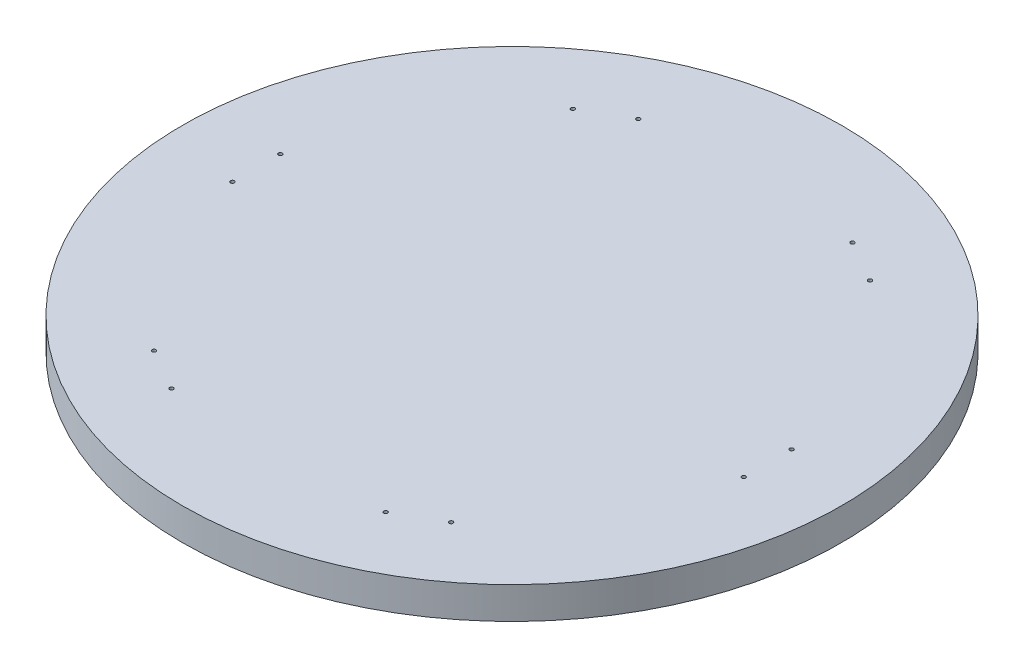
SolidWorks part; units mm, degrees
ref_plane "Front Plane" through (0, 0, 0) normal (0, 0, 1) x (1, 0, 0)
ref_plane "Top Plane" through (0, 0, 0) normal (0, 1, 0) x (1, 0, 0)
ref_plane "Right Plane" through (0, 0, 0) normal (1, 0, 0) x (0, 0, -1)
sketch "Sketch1" plane through (0, 0, 0) normal (0, 1, 0) x (1, 0, 0)
  circle A0 centre (0, 0) radius 261.9375
extrude "Boss-Extrude1" add sketch "Sketch1" along normal blind 25.4
sketch "Sketch6" plane through (0, 0, 0) normal (0, -1, 0) x (1, 0, 0)
  line L0 (203.2, 19.05) -> (203.2, -19.05) construction
  line L1 (215.9, 19.05) -> (215.9, -19.05)
  line L2 (190.5, 19.05) -> (190.5, -19.05)
  line L3 (203.2, -16.5451) -> (201.0307, -17.7976) construction
  line L4 (201.0307, -17.7976) -> (201.0307, -20.3024) construction
  line L5 (201.0307, -20.3024) -> (203.2, -21.5549) construction
  line L6 (203.2, -21.5549) -> (205.3693, -20.3024) construction
  line L7 (205.3693, -20.3024) -> (205.3693, -17.7976) construction
  line L8 (205.3693, -17.7976) -> (203.2, -16.5451) construction
  line L9 (203.2, 22.1294) -> (201.0307, 20.8769) construction
  line L10 (201.0307, 20.8769) -> (201.0307, 18.372) construction
  line L11 (201.0307, 18.372) -> (203.2, 17.1196) construction
  line L12 (203.2, 17.1196) -> (205.3693, 18.372) construction
  line L13 (205.3693, 18.372) -> (205.3693, 20.8769) construction
  line L14 (205.3693, 20.8769) -> (203.2, 22.1294) construction
  line L15 (0, 0) -> (203.2, 0) construction
  line L16 (87.2715, -184.2489) -> (85.1022, -182.9965) construction
  line L17 (85.1022, -182.9965) -> (82.9329, -184.2489) construction
  line L18 (82.9329, -184.2489) -> (82.9329, -186.7538) construction
  line L19 (82.9329, -186.7538) -> (85.1022, -188.0063) construction
  line L20 (85.1022, -188.0063) -> (87.2715, -186.7538) construction
  line L21 (87.2715, -186.7538) -> (87.2715, -184.2489) construction
  line L22 (120.7646, -164.9117) -> (118.5953, -163.6592) construction
  line L23 (118.5953, -163.6592) -> (116.426, -164.9117) construction
  line L24 (116.426, -164.9117) -> (116.426, -167.4166) construction
  line L25 (116.426, -167.4166) -> (118.5953, -168.669) construction
  line L26 (118.5953, -168.669) -> (120.7646, -167.4166) construction
  line L27 (120.7646, -167.4166) -> (120.7646, -164.9117) construction
  line L28 (0, 0) -> (101.6, -175.9764) construction
  line L29 (118.0978, -166.4514) -> (85.1022, -185.5014) construction
  line L30 (124.4478, -177.4499) -> (91.4522, -196.4999)
  line L31 (111.7478, -155.4528) -> (78.7522, -174.5028)
  line L32 (-115.9285, -167.7038) -> (-115.9285, -165.1989) construction
  line L33 (-115.9285, -165.1989) -> (-118.0978, -163.9465) construction
  line L34 (-118.0978, -163.9465) -> (-120.2671, -165.1989) construction
  line L35 (-120.2671, -165.1989) -> (-120.2671, -167.7038) construction
  line L36 (-120.2671, -167.7038) -> (-118.0978, -168.9563) construction
  line L37 (-118.0978, -168.9563) -> (-115.9285, -167.7038) construction
  line L38 (-82.4354, -187.0411) -> (-82.4354, -184.5362) construction
  line L39 (-82.4354, -184.5362) -> (-84.6047, -183.2837) construction
  line L40 (-84.6047, -183.2837) -> (-86.774, -184.5362) construction
  line L41 (-86.774, -184.5362) -> (-86.774, -187.0411) construction
  line L42 (-86.774, -187.0411) -> (-84.6047, -188.2935) construction
  line L43 (-84.6047, -188.2935) -> (-82.4354, -187.0411) construction
  line L44 (0, 0) -> (-101.6, -175.9764) construction
  line L45 (-85.1022, -185.5014) -> (-118.0978, -166.4514) construction
  line L46 (-91.4522, -196.4999) -> (-124.4478, -177.4499)
  line L47 (-78.7522, -174.5028) -> (-111.7478, -155.4528)
  line L48 (-203.2, 16.5451) -> (-201.0307, 17.7976) construction
  line L49 (-201.0307, 17.7976) -> (-201.0307, 20.3024) construction
  line L50 (-201.0307, 20.3024) -> (-203.2, 21.5549) construction
  line L51 (-203.2, 21.5549) -> (-205.3693, 20.3024) construction
  line L52 (-205.3693, 20.3024) -> (-205.3693, 17.7976) construction
  line L53 (-205.3693, 17.7976) -> (-203.2, 16.5451) construction
  line L54 (-203.2, -22.1294) -> (-201.0307, -20.8769) construction
  line L55 (-201.0307, -20.8769) -> (-201.0307, -18.372) construction
  line L56 (-201.0307, -18.372) -> (-203.2, -17.1196) construction
  line L57 (-203.2, -17.1196) -> (-205.3693, -18.372) construction
  line L58 (-205.3693, -18.372) -> (-205.3693, -20.8769) construction
  line L59 (-205.3693, -20.8769) -> (-203.2, -22.1294) construction
  line L60 (0, 0) -> (-203.2, 0) construction
  line L61 (-203.2, -19.05) -> (-203.2, 19.05) construction
  line L62 (-215.9, -19.05) -> (-215.9, 19.05)
  line L63 (-190.5, -19.05) -> (-190.5, 19.05)
  line L64 (-87.2715, 184.2489) -> (-85.1022, 182.9965) construction
  line L65 (-85.1022, 182.9965) -> (-82.9329, 184.2489) construction
  line L66 (-82.9329, 184.2489) -> (-82.9329, 186.7538) construction
  line L67 (-82.9329, 186.7538) -> (-85.1022, 188.0063) construction
  line L68 (-85.1022, 188.0063) -> (-87.2715, 186.7538) construction
  line L69 (-87.2715, 186.7538) -> (-87.2715, 184.2489) construction
  line L70 (-120.7646, 164.9117) -> (-118.5953, 163.6592) construction
  line L71 (-118.5953, 163.6592) -> (-116.426, 164.9117) construction
  line L72 (-116.426, 164.9117) -> (-116.426, 167.4166) construction
  line L73 (-116.426, 167.4166) -> (-118.5953, 168.669) construction
  line L74 (-118.5953, 168.669) -> (-120.7646, 167.4166) construction
  line L75 (-120.7646, 167.4166) -> (-120.7646, 164.9117) construction
  line L76 (0, 0) -> (-101.6, 175.9764) construction
  line L77 (-118.0978, 166.4514) -> (-85.1022, 185.5014) construction
  line L78 (-124.4478, 177.4499) -> (-91.4522, 196.4999)
  line L79 (-111.7478, 155.4528) -> (-78.7522, 174.5028)
  line L80 (115.9285, 167.7038) -> (115.9285, 165.1989) construction
  line L81 (115.9285, 165.1989) -> (118.0978, 163.9465) construction
  line L82 (118.0978, 163.9465) -> (120.2671, 165.1989) construction
  line L83 (120.2671, 165.1989) -> (120.2671, 167.7038) construction
  line L84 (120.2671, 167.7038) -> (118.0978, 168.9563) construction
  line L85 (118.0978, 168.9563) -> (115.9285, 167.7038) construction
  line L86 (82.4354, 187.0411) -> (82.4354, 184.5362) construction
  line L87 (82.4354, 184.5362) -> (84.6047, 183.2837) construction
  line L88 (84.6047, 183.2837) -> (86.774, 184.5362) construction
  line L89 (86.774, 184.5362) -> (86.774, 187.0411) construction
  line L90 (86.774, 187.0411) -> (84.6047, 188.2935) construction
  line L91 (84.6047, 188.2935) -> (82.4354, 187.0411) construction
  line L92 (0, 0) -> (101.6, 175.9764) construction
  line L93 (85.1022, 185.5014) -> (118.0978, 166.4514) construction
  line L94 (91.4522, 196.4999) -> (124.4478, 177.4499)
  line L95 (78.7522, 174.5028) -> (111.7478, 155.4528)
  arc A0 (215.9, 19.05) -> (190.5, 19.05) centre (203.2, 19.05) ccw
  arc A1 (190.5, -19.05) -> (215.9, -19.05) centre (203.2, -19.05) ccw
  circle A2 centre (203.2, -19.05) radius 2.1693 construction
  circle A3 centre (203.2, 19.6245) radius 2.1693 construction
  circle A4 centre (203.2, -19.05) radius 1.524 construction
  circle A5 centre (203.2, 19.6245) radius 1.524 construction
  circle A6 centre (85.1022, -185.5014) radius 2.1693 construction
  circle A7 centre (118.5953, -166.1641) radius 2.1693 construction
  circle A8 centre (85.1022, -185.5014) radius 1.524 construction
  circle A9 centre (118.5953, -166.1641) radius 1.524 construction
  arc A10 (124.4478, -177.4499) -> (111.7478, -155.4528) centre (118.0978, -166.4514) ccw
  arc A11 (78.7522, -174.5028) -> (91.4522, -196.4999) centre (85.1022, -185.5014) ccw
  circle A12 centre (-118.0978, -166.4514) radius 2.1693 construction
  circle A13 centre (-84.6047, -185.7886) radius 2.1693 construction
  circle A14 centre (-118.0978, -166.4514) radius 1.524 construction
  circle A15 centre (-84.6047, -185.7886) radius 1.524 construction
  arc A16 (-91.4522, -196.4999) -> (-78.7522, -174.5028) centre (-85.1022, -185.5014) ccw
  arc A17 (-111.7478, -155.4528) -> (-124.4478, -177.4499) centre (-118.0978, -166.4514) ccw
  circle A18 centre (-203.2, 19.05) radius 2.1693 construction
  circle A19 centre (-203.2, -19.6245) radius 2.1693 construction
  circle A20 centre (-203.2, 19.05) radius 1.524 construction
  circle A21 centre (-203.2, -19.6245) radius 1.524 construction
  arc A22 (-215.9, -19.05) -> (-190.5, -19.05) centre (-203.2, -19.05) ccw
  arc A23 (-190.5, 19.05) -> (-215.9, 19.05) centre (-203.2, 19.05) ccw
  circle A24 centre (-85.1022, 185.5014) radius 2.1693 construction
  circle A25 centre (-118.5953, 166.1641) radius 2.1693 construction
  circle A26 centre (-85.1022, 185.5014) radius 1.524 construction
  circle A27 centre (-118.5953, 166.1641) radius 1.524 construction
  arc A28 (-124.4478, 177.4499) -> (-111.7478, 155.4528) centre (-118.0978, 166.4514) ccw
  arc A29 (-78.7522, 174.5028) -> (-91.4522, 196.4999) centre (-85.1022, 185.5014) ccw
  circle A30 centre (118.0978, 166.4514) radius 2.1693 construction
  circle A31 centre (84.6047, 185.7886) radius 2.1693 construction
  circle A32 centre (118.0978, 166.4514) radius 1.524 construction
  circle A33 centre (84.6047, 185.7886) radius 1.524 construction
  arc A34 (91.4522, 196.4999) -> (78.7522, 174.5028) centre (85.1022, 185.5014) ccw
  arc A35 (111.7478, 155.4528) -> (124.4478, 177.4499) centre (118.0978, 166.4514) ccw
  point P2 (203.2, 0)
  point P32 (101.6, -175.9764)
  point P58 (-101.6, -175.9764)
  point P84 (-203.2, 0)
  point P110 (-101.6, 175.9764)
  point P136 (101.6, 175.9764)
  point P160 (0, 0)
  dimension "D1" = 6
extrude "Cut-Extrude4" cut sketch "Sketch6" against normal blind 12.7
sketch "Sketch9" plane through (0, 0, 0) normal (0, -1, 0) x (1, 0, 0)
  circle A0 centre (0, 0) radius 25.4
extrude "Boss-Extrude2" add sketch "Sketch9" along normal blind 10.16 and the other way through all
sketch "Sketch10" plane through (0, -10.16, 0) normal (0, -1, 0) x (1, 0, 0)
  line L0 (0, -2.032) -> (0, 1.524) construction
  line L1 (-1.344, 1.524) -> (1.344, 1.524)
  line L2 (-2.032, 0) -> (-2.032, 1.524)
  line L3 (-2.032, 1.524) -> (-1.344, 1.524)
  line L4 (2.032, 0) -> (2.032, 1.524)
  line L5 (2.032, 1.524) -> (1.344, 1.524)
  arc A0 (-2.032, 0) -> (2.032, 0) centre (0, 0) ccw
extrude "Cut-Extrude7" cut sketch "Sketch10" against normal blind 19.05
sketch "Sketch11" plane through (0, 0, 0) normal (0, -1, 0) x (1, 0, 0)
  line L0 (0, 0) -> (-11.1642, -177.4492) construction
  line L1 (0, 0) -> (0, -291.8902) construction
  line L2 (0, 0) -> (11.1642, -177.4492) construction
  line L3 (-33.3164, -174.6507) -> (-22.2403, -176.0499) construction
  line L4 (-11.1642, -177.4492) -> (0, -177.4492) construction
  line L5 (0, -177.4492) -> (11.1642, -177.4492) construction
  line L6 (-22.2403, -176.0499) -> (-11.1642, -177.4492) construction
  line L7 (-54.9432, -169.0978) -> (-44.1298, -171.8743) construction
  line L8 (-44.1298, -171.8743) -> (-33.3164, -174.6507) construction
  line L9 (-75.7036, -160.8782) -> (-65.3234, -164.988) construction
  line L10 (-65.3234, -164.988) -> (-54.9432, -169.0978) construction
  line L11 (-95.27, -150.1215) -> (-85.4868, -155.4999) construction
  line L12 (-85.4868, -155.4999) -> (-75.7036, -160.8782) construction
  line L13 (-113.334, -136.9973) -> (-104.302, -143.5594) construction
  line L14 (-104.302, -143.5594) -> (-95.27, -150.1215) construction
  line L15 (-129.6106, -121.7125) -> (-121.4723, -129.3549) construction
  line L16 (-121.4723, -129.3549) -> (-113.334, -136.9973) construction
  line L17 (-143.8432, -104.5082) -> (-136.7269, -113.1103) construction
  line L18 (-136.7269, -113.1103) -> (-129.6106, -121.7125) construction
  line L19 (-155.8073, -85.6558) -> (-149.8253, -95.082) construction
  line L20 (-149.8253, -95.082) -> (-143.8432, -104.5082) construction
  line L21 (-165.3143, -65.4525) -> (-160.5608, -75.5542) construction
  line L22 (-160.5608, -75.5542) -> (-155.8073, -85.6558) construction
  line L23 (-172.2141, -44.2171) -> (-168.7642, -54.8348) construction
  line L24 (-168.7642, -54.8348) -> (-165.3143, -65.4525) construction
  line L25 (-176.398, -22.2842) -> (-174.306, -33.2507) construction
  line L26 (-174.306, -33.2507) -> (-172.2141, -44.2171) construction
  line L27 (-177.8, 0) -> (-177.099, -11.1421) construction
  line L28 (-177.099, -11.1421) -> (-176.398, -22.2842) construction
  line L29 (-176.398, 22.2842) -> (-177.099, 11.1421) construction
  line L30 (-177.099, 11.1421) -> (-177.8, 0) construction
  line L31 (-172.2141, 44.2171) -> (-174.306, 33.2507) construction
  line L32 (-174.306, 33.2507) -> (-176.398, 22.2842) construction
  line L33 (-165.3143, 65.4525) -> (-168.7642, 54.8348) construction
  line L34 (-168.7642, 54.8348) -> (-172.2141, 44.2171) construction
  line L35 (-155.8073, 85.6558) -> (-160.5608, 75.5542) construction
  line L36 (-160.5608, 75.5542) -> (-165.3143, 65.4525) construction
  line L37 (-143.8432, 104.5082) -> (-149.8253, 95.082) construction
  line L38 (-149.8253, 95.082) -> (-155.8073, 85.6558) construction
  line L39 (-129.6106, 121.7125) -> (-136.7269, 113.1103) construction
  line L40 (-136.7269, 113.1103) -> (-143.8432, 104.5082) construction
  line L41 (-113.334, 136.9973) -> (-121.4723, 129.3549) construction
  line L42 (-121.4723, 129.3549) -> (-129.6106, 121.7125) construction
  line L43 (-95.27, 150.1215) -> (-104.302, 143.5594) construction
  line L44 (-104.302, 143.5594) -> (-113.334, 136.9973) construction
  line L45 (-75.7036, 160.8782) -> (-85.4868, 155.4999) construction
  line L46 (-85.4868, 155.4999) -> (-95.27, 150.1215) construction
  line L47 (-54.9432, 169.0978) -> (-65.3234, 164.988) construction
  line L48 (-65.3234, 164.988) -> (-75.7036, 160.8782) construction
  line L49 (-33.3164, 174.6507) -> (-44.1298, 171.8743) construction
  line L50 (-44.1298, 171.8743) -> (-54.9432, 169.0978) construction
  line L51 (-11.1642, 177.4492) -> (-22.2403, 176.0499) construction
  line L52 (-22.2403, 176.0499) -> (-33.3164, 174.6507) construction
  line L53 (11.1642, 177.4492) -> (0, 177.4492) construction
  line L54 (0, 177.4492) -> (-11.1642, 177.4492) construction
  line L55 (33.3164, 174.6507) -> (22.2403, 176.0499) construction
  line L56 (22.2403, 176.0499) -> (11.1642, 177.4492) construction
  line L57 (54.9432, 169.0978) -> (44.1298, 171.8743) construction
  line L58 (44.1298, 171.8743) -> (33.3164, 174.6507) construction
  line L59 (75.7036, 160.8782) -> (65.3234, 164.988) construction
  line L60 (65.3234, 164.988) -> (54.9432, 169.0978) construction
  line L61 (95.27, 150.1215) -> (85.4868, 155.4999) construction
  line L62 (85.4868, 155.4999) -> (75.7036, 160.8782) construction
  line L63 (113.334, 136.9973) -> (104.302, 143.5594) construction
  line L64 (104.302, 143.5594) -> (95.27, 150.1215) construction
  line L65 (129.6106, 121.7125) -> (121.4723, 129.3549) construction
  line L66 (121.4723, 129.3549) -> (113.334, 136.9973) construction
  line L67 (143.8432, 104.5082) -> (136.7269, 113.1103) construction
  line L68 (136.7269, 113.1103) -> (129.6106, 121.7125) construction
  line L69 (155.8073, 85.6558) -> (149.8253, 95.082) construction
  line L70 (149.8253, 95.082) -> (143.8432, 104.5082) construction
  line L71 (165.3143, 65.4525) -> (160.5608, 75.5542) construction
  line L72 (160.5608, 75.5542) -> (155.8073, 85.6558) construction
  line L73 (172.2141, 44.2171) -> (168.7642, 54.8348) construction
  line L74 (168.7642, 54.8348) -> (165.3143, 65.4525) construction
  line L75 (176.398, 22.2842) -> (174.306, 33.2507) construction
  line L76 (174.306, 33.2507) -> (172.2141, 44.2171) construction
  line L77 (177.8, 0) -> (177.099, 11.1421) construction
  line L78 (177.099, 11.1421) -> (176.398, 22.2842) construction
  line L79 (176.398, -22.2842) -> (177.099, -11.1421) construction
  line L80 (177.099, -11.1421) -> (177.8, 0) construction
  line L81 (172.2141, -44.2171) -> (174.306, -33.2507) construction
  line L82 (174.306, -33.2507) -> (176.398, -22.2842) construction
  line L83 (165.3143, -65.4525) -> (168.7642, -54.8348) construction
  line L84 (168.7642, -54.8348) -> (172.2141, -44.2171) construction
  line L85 (155.8073, -85.6558) -> (160.5608, -75.5542) construction
  line L86 (160.5608, -75.5542) -> (165.3143, -65.4525) construction
  line L87 (143.8432, -104.5082) -> (149.8253, -95.082) construction
  line L88 (149.8253, -95.082) -> (155.8073, -85.6558) construction
  line L89 (129.6106, -121.7125) -> (136.7269, -113.1103) construction
  line L90 (136.7269, -113.1103) -> (143.8432, -104.5082) construction
  line L91 (113.334, -136.9973) -> (121.4723, -129.3549) construction
  line L92 (121.4723, -129.3549) -> (129.6106, -121.7125) construction
  line L93 (95.27, -150.1215) -> (104.302, -143.5594) construction
  line L94 (104.302, -143.5594) -> (113.334, -136.9973) construction
  line L95 (75.7036, -160.8782) -> (85.4868, -155.4999) construction
  line L96 (85.4868, -155.4999) -> (95.27, -150.1215) construction
  line L97 (54.9432, -169.0978) -> (65.3234, -164.988) construction
  line L98 (65.3234, -164.988) -> (75.7036, -160.8782) construction
  line L99 (33.3164, -174.6507) -> (44.1298, -171.8743) construction
  line L100 (44.1298, -171.8743) -> (54.9432, -169.0978) construction
  line L101 (11.1642, -177.4492) -> (22.2403, -176.0499) construction
  line L102 (22.2403, -176.0499) -> (33.3164, -174.6507) construction
  circle A0 centre (0, 0) radius 177.8 construction
  arc A1 (0, -177.4492) -> (-11.1201, -176.7495) centre (-5.5821, -177.4492) ccw
  arc A2 (0, -177.4492) -> (11.1201, -176.7495) centre (5.5821, -177.4492) ccw
  arc A3 (-22.2403, -176.0499) -> (-33.185, -173.9621) centre (-27.7783, -175.3503) ccw
  arc A4 (-22.2403, -176.0499) -> (-11.1201, -176.7495) centre (-16.7022, -176.7495) ccw
  arc A5 (-44.1298, -171.8743) -> (-54.7266, -168.4312) centre (-49.5365, -170.4861) ccw
  arc A6 (-44.1298, -171.8743) -> (-33.185, -173.9621) centre (-38.7231, -173.2625) ccw
  arc A7 (-65.3234, -164.988) -> (-75.4051, -160.244) centre (-70.5135, -162.9331) ccw
  arc A8 (-65.3234, -164.988) -> (-54.7266, -168.4312) centre (-60.1333, -167.0429) ccw
  arc A9 (-85.4868, -155.4999) -> (-94.8944, -149.5296) centre (-90.3784, -152.8107) ccw
  arc A10 (-85.4868, -155.4999) -> (-75.4051, -160.244) centre (-80.5952, -158.1891) ccw
  arc A11 (-104.302, -143.5594) -> (-112.8871, -136.4571) centre (-108.818, -140.2783) ccw
  arc A12 (-104.302, -143.5594) -> (-94.8944, -149.5296) centre (-99.786, -146.8404) ccw
  arc A13 (-121.4723, -129.3549) -> (-129.0996, -121.2326) centre (-125.5415, -125.5337) ccw
  arc A14 (-121.4723, -129.3549) -> (-112.8871, -136.4571) centre (-117.4031, -133.1761) ccw
  arc A15 (-136.7269, -113.1103) -> (-143.2761, -104.0962) centre (-140.2851, -108.8093) ccw
  arc A16 (-136.7269, -113.1103) -> (-129.0996, -121.2326) centre (-133.1688, -117.4114) ccw
  arc A17 (-149.8253, -95.082) -> (-155.193, -85.3181) centre (-152.8163, -90.3689) ccw
  arc A18 (-149.8253, -95.082) -> (-143.2761, -104.0962) centre (-146.8342, -99.7951) ccw
  arc A19 (-160.5608, -75.5542) -> (-164.6625, -65.1945) centre (-162.9375, -70.5034) ccw
  arc A20 (-160.5608, -75.5542) -> (-155.193, -85.3181) centre (-158.1841, -80.605) ccw
  arc A21 (-168.7642, -54.8348) -> (-171.5351, -44.0427) centre (-170.4891, -49.5259) ccw
  arc A22 (-168.7642, -54.8348) -> (-164.6625, -65.1945) centre (-167.0392, -60.1437) ccw
  arc A23 (-174.306, -33.2507) -> (-175.7025, -22.1964) centre (-175.352, -27.7675) ccw
  arc A24 (-174.306, -33.2507) -> (-171.5351, -44.0427) centre (-173.2601, -38.7339) ccw
  arc A25 (-177.099, -11.1421) -> (-177.099, 0) centre (-177.4495, -5.5711) ccw
  arc A26 (-177.099, -11.1421) -> (-175.7025, -22.1964) centre (-176.7485, -16.7132) ccw
  arc A27 (-177.099, 11.1421) -> (-175.7025, 22.1964) centre (-176.7485, 16.7132) ccw
  arc A28 (-177.099, 11.1421) -> (-177.099, 0) centre (-177.4495, 5.5711) ccw
  arc A29 (-174.306, 33.2507) -> (-171.5351, 44.0427) centre (-173.2601, 38.7339) ccw
  arc A30 (-174.306, 33.2507) -> (-175.7025, 22.1964) centre (-175.352, 27.7675) ccw
  arc A31 (-168.7642, 54.8348) -> (-164.6625, 65.1945) centre (-167.0392, 60.1437) ccw
  arc A32 (-168.7642, 54.8348) -> (-171.5351, 44.0427) centre (-170.4891, 49.5259) ccw
  arc A33 (-160.5608, 75.5542) -> (-155.193, 85.3181) centre (-158.1841, 80.605) ccw
  arc A34 (-160.5608, 75.5542) -> (-164.6625, 65.1945) centre (-162.9375, 70.5034) ccw
  arc A35 (-149.8253, 95.082) -> (-143.2761, 104.0962) centre (-146.8342, 99.7951) ccw
  arc A36 (-149.8253, 95.082) -> (-155.193, 85.3181) centre (-152.8163, 90.3689) ccw
  arc A37 (-136.7269, 113.1103) -> (-129.0996, 121.2326) centre (-133.1688, 117.4114) ccw
  arc A38 (-136.7269, 113.1103) -> (-143.2761, 104.0962) centre (-140.2851, 108.8093) ccw
  arc A39 (-121.4723, 129.3549) -> (-112.8871, 136.4571) centre (-117.4031, 133.1761) ccw
  arc A40 (-121.4723, 129.3549) -> (-129.0996, 121.2326) centre (-125.5415, 125.5337) ccw
  arc A41 (-104.302, 143.5594) -> (-94.8944, 149.5296) centre (-99.786, 146.8404) ccw
  arc A42 (-104.302, 143.5594) -> (-112.8871, 136.4571) centre (-108.818, 140.2783) ccw
  arc A43 (-85.4868, 155.4999) -> (-75.4051, 160.244) centre (-80.5952, 158.1891) ccw
  arc A44 (-85.4868, 155.4999) -> (-94.8944, 149.5296) centre (-90.3784, 152.8107) ccw
  arc A45 (-65.3234, 164.988) -> (-54.7266, 168.4312) centre (-60.1333, 167.0429) ccw
  arc A46 (-65.3234, 164.988) -> (-75.4051, 160.244) centre (-70.5135, 162.9331) ccw
  arc A47 (-44.1298, 171.8743) -> (-33.185, 173.9621) centre (-38.7231, 173.2625) ccw
  arc A48 (-44.1298, 171.8743) -> (-54.7266, 168.4312) centre (-49.5365, 170.4861) ccw
  arc A49 (-22.2403, 176.0499) -> (-11.1201, 176.7495) centre (-16.7022, 176.7495) ccw
  arc A50 (-22.2403, 176.0499) -> (-33.185, 173.9621) centre (-27.7783, 175.3503) ccw
  arc A51 (0, 177.4492) -> (11.1201, 176.7495) centre (5.5821, 177.4492) ccw
  arc A52 (0, 177.4492) -> (-11.1201, 176.7495) centre (-5.5821, 177.4492) ccw
  arc A53 (22.2403, 176.0499) -> (33.185, 173.9621) centre (27.7783, 175.3503) ccw
  arc A54 (22.2403, 176.0499) -> (11.1201, 176.7495) centre (16.7022, 176.7495) ccw
  arc A55 (44.1298, 171.8743) -> (54.7266, 168.4312) centre (49.5365, 170.4861) ccw
  arc A56 (44.1298, 171.8743) -> (33.185, 173.9621) centre (38.7231, 173.2625) ccw
  arc A57 (65.3234, 164.988) -> (75.4051, 160.244) centre (70.5135, 162.9331) ccw
  arc A58 (65.3234, 164.988) -> (54.7266, 168.4312) centre (60.1333, 167.0429) ccw
  arc A59 (85.4868, 155.4999) -> (94.8944, 149.5296) centre (90.3784, 152.8107) ccw
  arc A60 (85.4868, 155.4999) -> (75.4051, 160.244) centre (80.5952, 158.1891) ccw
  arc A61 (104.302, 143.5594) -> (112.8871, 136.4571) centre (108.818, 140.2783) ccw
  arc A62 (104.302, 143.5594) -> (94.8944, 149.5296) centre (99.786, 146.8404) ccw
  arc A63 (121.4723, 129.3549) -> (129.0996, 121.2326) centre (125.5415, 125.5337) ccw
  arc A64 (121.4723, 129.3549) -> (112.8871, 136.4571) centre (117.4031, 133.1761) ccw
  arc A65 (136.7269, 113.1103) -> (143.2761, 104.0962) centre (140.2851, 108.8093) ccw
  arc A66 (136.7269, 113.1103) -> (129.0996, 121.2326) centre (133.1688, 117.4114) ccw
  arc A67 (149.8253, 95.082) -> (155.193, 85.3181) centre (152.8163, 90.3689) ccw
  arc A68 (149.8253, 95.082) -> (143.2761, 104.0962) centre (146.8342, 99.7951) ccw
  arc A69 (160.5608, 75.5542) -> (164.6625, 65.1945) centre (162.9375, 70.5034) ccw
  arc A70 (160.5608, 75.5542) -> (155.193, 85.3181) centre (158.1841, 80.605) ccw
  arc A71 (168.7642, 54.8348) -> (171.5351, 44.0427) centre (170.4891, 49.5259) ccw
  arc A72 (168.7642, 54.8348) -> (164.6625, 65.1945) centre (167.0392, 60.1437) ccw
  arc A73 (174.306, 33.2507) -> (175.7025, 22.1964) centre (175.352, 27.7675) ccw
  arc A74 (174.306, 33.2507) -> (171.5351, 44.0427) centre (173.2601, 38.7339) ccw
  arc A75 (177.099, 11.1421) -> (177.099, 0) centre (177.4495, 5.5711) ccw
  arc A76 (177.099, 11.1421) -> (175.7025, 22.1964) centre (176.7485, 16.7132) ccw
  arc A77 (177.099, -11.1421) -> (175.7025, -22.1964) centre (176.7485, -16.7132) ccw
  arc A78 (177.099, -11.1421) -> (177.099, 0) centre (177.4495, -5.5711) ccw
  arc A79 (174.306, -33.2507) -> (171.5351, -44.0427) centre (173.2601, -38.7339) ccw
  arc A80 (174.306, -33.2507) -> (175.7025, -22.1964) centre (175.352, -27.7675) ccw
  arc A81 (168.7642, -54.8348) -> (164.6625, -65.1945) centre (167.0392, -60.1437) ccw
  arc A82 (168.7642, -54.8348) -> (171.5351, -44.0427) centre (170.4891, -49.5259) ccw
  arc A83 (160.5608, -75.5542) -> (155.193, -85.3181) centre (158.1841, -80.605) ccw
  arc A84 (160.5608, -75.5542) -> (164.6625, -65.1945) centre (162.9375, -70.5034) ccw
  arc A85 (149.8253, -95.082) -> (143.2761, -104.0962) centre (146.8342, -99.7951) ccw
  arc A86 (149.8253, -95.082) -> (155.193, -85.3181) centre (152.8163, -90.3689) ccw
  arc A87 (136.7269, -113.1103) -> (129.0996, -121.2326) centre (133.1688, -117.4114) ccw
  arc A88 (136.7269, -113.1103) -> (143.2761, -104.0962) centre (140.2851, -108.8093) ccw
  arc A89 (121.4723, -129.3549) -> (112.8871, -136.4571) centre (117.4031, -133.1761) ccw
  arc A90 (121.4723, -129.3549) -> (129.0996, -121.2326) centre (125.5415, -125.5337) ccw
  arc A91 (104.302, -143.5594) -> (94.8944, -149.5296) centre (99.786, -146.8404) ccw
  arc A92 (104.302, -143.5594) -> (112.8871, -136.4571) centre (108.818, -140.2783) ccw
  arc A93 (85.4868, -155.4999) -> (75.4051, -160.244) centre (80.5952, -158.1891) ccw
  arc A94 (85.4868, -155.4999) -> (94.8944, -149.5296) centre (90.3784, -152.8107) ccw
  arc A95 (65.3234, -164.988) -> (54.7266, -168.4312) centre (60.1333, -167.0429) ccw
  arc A96 (65.3234, -164.988) -> (75.4051, -160.244) centre (70.5135, -162.9331) ccw
  arc A97 (44.1298, -171.8743) -> (33.185, -173.9621) centre (38.7231, -173.2625) ccw
  arc A98 (44.1298, -171.8743) -> (54.7266, -168.4312) centre (49.5365, -170.4861) ccw
  arc A99 (22.2403, -176.0499) -> (11.1201, -176.7495) centre (16.7022, -176.7495) ccw
  arc A100 (22.2403, -176.0499) -> (33.185, -173.9621) centre (27.7783, -175.3503) ccw
  circle A101 centre (0, 0) radius 27.7675
  point P356 (0, 0)
  dimension "D1" = 50
extrude "Cut-Extrude9" cut sketch "Sketch11" against normal blind 6.35
sketch "Sketch12" plane through (0, 12.7, 0) normal (0, -1, 0) x (1, 0, 0)
  line L0 (203.2, 19.05) -> (203.2, -19.05) construction
  line L1 (215.9, 19.05) -> (215.9, -19.05) construction
  line L2 (190.5, 19.05) -> (190.5, -19.05) construction
  line L3 (203.2, -16.5451) -> (201.0307, -17.7975) construction
  line L4 (201.0307, -17.7975) -> (201.0307, -20.3024) construction
  line L5 (201.0307, -20.3024) -> (203.2, -21.5549) construction
  line L6 (203.2, -21.5549) -> (205.3693, -20.3024) construction
  line L7 (205.3693, -20.3024) -> (205.3693, -17.7975) construction
  line L8 (205.3693, -17.7975) -> (203.2, -16.5451) construction
  line L9 (203.2, 21.5549) -> (201.0307, 20.3025) construction
  line L10 (201.0307, 20.3025) -> (201.0307, 17.7976) construction
  line L11 (201.0307, 17.7976) -> (203.2, 16.5451) construction
  line L12 (203.2, 16.5451) -> (205.3693, 17.7976) construction
  line L13 (205.3693, 17.7976) -> (205.3693, 20.3025) construction
  line L14 (205.3693, 20.3025) -> (203.2, 21.5549) construction
  line L15 (190.5, -19.05) -> (203.2, -19.05) construction
  line L16 (87.2715, -184.2489) -> (85.1022, -182.9965) construction
  line L17 (85.1022, -182.9965) -> (82.9329, -184.2489) construction
  line L18 (82.9329, -184.2489) -> (82.9329, -186.7538) construction
  line L19 (82.9329, -186.7538) -> (85.1022, -188.0062) construction
  line L20 (85.1022, -188.0062) -> (87.2715, -186.7538) construction
  line L21 (87.2715, -186.7538) -> (87.2715, -184.2489) construction
  line L22 (120.2671, -165.1989) -> (118.0978, -163.9465) construction
  line L23 (118.0978, -163.9465) -> (115.9285, -165.1989) construction
  line L24 (115.9285, -165.1989) -> (115.9285, -167.7038) construction
  line L25 (115.9285, -167.7038) -> (118.0978, -168.9562) construction
  line L26 (118.0978, -168.9562) -> (120.2671, -167.7038) construction
  line L27 (120.2671, -167.7038) -> (120.2671, -165.1989) construction
  line L28 (78.7522, -174.5028) -> (85.1022, -185.5014) construction
  line L29 (118.0978, -166.4514) -> (85.1022, -185.5014) construction
  line L30 (124.4478, -177.4499) -> (91.4522, -196.4999) construction
  line L31 (111.7478, -155.4528) -> (78.7522, -174.5028) construction
  line L32 (-115.9285, -167.7038) -> (-115.9285, -165.1989) construction
  line L33 (-115.9285, -165.1989) -> (-118.0978, -163.9465) construction
  line L34 (-118.0978, -163.9465) -> (-120.2671, -165.1989) construction
  line L35 (-120.2671, -165.1989) -> (-120.2671, -167.7038) construction
  line L36 (-120.2671, -167.7038) -> (-118.0978, -168.9563) construction
  line L37 (-118.0978, -168.9563) -> (-115.9285, -167.7038) construction
  line L38 (-82.9329, -186.7538) -> (-82.9329, -184.2489) construction
  line L39 (-82.9329, -184.2489) -> (-85.1022, -182.9965) construction
  line L40 (-85.1022, -182.9965) -> (-87.2715, -184.2489) construction
  line L41 (-87.2715, -184.2489) -> (-87.2715, -186.7538) construction
  line L42 (-87.2715, -186.7538) -> (-85.1022, -188.0063) construction
  line L43 (-85.1022, -188.0063) -> (-82.9329, -186.7538) construction
  line L44 (-111.7478, -155.4528) -> (-118.0978, -166.4514) construction
  line L45 (-85.1022, -185.5014) -> (-118.0978, -166.4514) construction
  line L46 (-91.4522, -196.4999) -> (-124.4478, -177.4499) construction
  line L47 (-78.7522, -174.5028) -> (-111.7478, -155.4528) construction
  line L48 (-203.2, 16.5451) -> (-201.0307, 17.7975) construction
  line L49 (-201.0307, 17.7975) -> (-201.0307, 20.3024) construction
  line L50 (-201.0307, 20.3024) -> (-203.2, 21.5549) construction
  line L51 (-203.2, 21.5549) -> (-205.3693, 20.3024) construction
  line L52 (-205.3693, 20.3024) -> (-205.3693, 17.7975) construction
  line L53 (-205.3693, 17.7975) -> (-203.2, 16.5451) construction
  line L54 (-203.2, -21.5549) -> (-201.0307, -20.3025) construction
  line L55 (-201.0307, -20.3025) -> (-201.0307, -17.7976) construction
  line L56 (-201.0307, -17.7976) -> (-203.2, -16.5451) construction
  line L57 (-203.2, -16.5451) -> (-205.3693, -17.7976) construction
  line L58 (-205.3693, -17.7976) -> (-205.3693, -20.3025) construction
  line L59 (-205.3693, -20.3025) -> (-203.2, -21.5549) construction
  line L60 (-190.5, 19.05) -> (-203.2, 19.05) construction
  line L61 (-203.2, -19.05) -> (-203.2, 19.05) construction
  line L62 (-215.9, -19.05) -> (-215.9, 19.05) construction
  line L63 (-190.5, -19.05) -> (-190.5, 19.05) construction
  line L64 (-87.2715, 184.2489) -> (-85.1022, 182.9965) construction
  line L65 (-85.1022, 182.9965) -> (-82.9329, 184.2489) construction
  line L66 (-82.9329, 184.2489) -> (-82.9329, 186.7538) construction
  line L67 (-82.9329, 186.7538) -> (-85.1022, 188.0062) construction
  line L68 (-85.1022, 188.0062) -> (-87.2715, 186.7538) construction
  line L69 (-87.2715, 186.7538) -> (-87.2715, 184.2489) construction
  line L70 (-120.2671, 165.1989) -> (-118.0978, 163.9465) construction
  line L71 (-118.0978, 163.9465) -> (-115.9285, 165.1989) construction
  line L72 (-115.9285, 165.1989) -> (-115.9285, 167.7038) construction
  line L73 (-115.9285, 167.7038) -> (-118.0978, 168.9562) construction
  line L74 (-118.0978, 168.9562) -> (-120.2671, 167.7038) construction
  line L75 (-120.2671, 167.7038) -> (-120.2671, 165.1989) construction
  line L76 (-78.7522, 174.5028) -> (-85.1022, 185.5014) construction
  line L77 (-118.0978, 166.4514) -> (-85.1022, 185.5014) construction
  line L78 (-124.4478, 177.4499) -> (-91.4522, 196.4999) construction
  line L79 (-111.7478, 155.4528) -> (-78.7522, 174.5028) construction
  line L80 (115.9285, 167.7038) -> (115.9285, 165.1989) construction
  line L81 (115.9285, 165.1989) -> (118.0978, 163.9465) construction
  line L82 (118.0978, 163.9465) -> (120.2671, 165.1989) construction
  line L83 (120.2671, 165.1989) -> (120.2671, 167.7038) construction
  line L84 (120.2671, 167.7038) -> (118.0978, 168.9563) construction
  line L85 (118.0978, 168.9563) -> (115.9285, 167.7038) construction
  line L86 (82.9329, 186.7538) -> (82.9329, 184.2489) construction
  line L87 (82.9329, 184.2489) -> (85.1022, 182.9965) construction
  line L88 (85.1022, 182.9965) -> (87.2715, 184.2489) construction
  line L89 (87.2715, 184.2489) -> (87.2715, 186.7538) construction
  line L90 (87.2715, 186.7538) -> (85.1022, 188.0063) construction
  line L91 (85.1022, 188.0063) -> (82.9329, 186.7538) construction
  line L92 (111.7478, 155.4528) -> (118.0978, 166.4514) construction
  line L93 (85.1022, 185.5014) -> (118.0978, 166.4514) construction
  line L94 (91.4522, 196.4999) -> (124.4478, 177.4499) construction
  line L95 (78.7522, 174.5028) -> (111.7478, 155.4528) construction
  line L96 (0, 0) -> (-101.6, 175.9764) construction
  arc A0 (215.9, 19.05) -> (190.5, 19.05) centre (203.2, 19.05) ccw construction
  arc A1 (190.5, -19.05) -> (215.9, -19.05) centre (203.2, -19.05) ccw construction
  circle A2 centre (203.2, -19.05) radius 2.1693 construction
  circle A3 centre (203.2, 19.05) radius 2.1693 construction
  circle A4 centre (203.2, -19.05) radius 1.524
  circle A5 centre (203.2, 19.05) radius 1.524
  circle A6 centre (85.1022, -185.5014) radius 1.524
  circle A7 centre (118.0978, -166.4514) radius 1.524
  circle A8 centre (85.1022, -185.5014) radius 2.1693 construction
  circle A9 centre (118.0978, -166.4514) radius 2.1693 construction
  arc A10 (124.4478, -177.4499) -> (111.7478, -155.4528) centre (118.0978, -166.4514) ccw construction
  arc A11 (78.7522, -174.5028) -> (91.4522, -196.4999) centre (85.1022, -185.5014) ccw construction
  circle A12 centre (-118.0978, -166.4514) radius 1.524
  circle A13 centre (-85.1022, -185.5014) radius 1.524
  circle A14 centre (-118.0978, -166.4514) radius 2.1693 construction
  circle A15 centre (-85.1022, -185.5014) radius 2.1693 construction
  arc A16 (-91.4522, -196.4999) -> (-78.7522, -174.5028) centre (-85.1022, -185.5014) ccw construction
  arc A17 (-111.7478, -155.4528) -> (-124.4478, -177.4499) centre (-118.0978, -166.4514) ccw construction
  circle A18 centre (-203.2, 19.05) radius 1.524
  circle A19 centre (-203.2, -19.05) radius 1.524
  circle A20 centre (-203.2, 19.05) radius 2.1693 construction
  circle A21 centre (-203.2, -19.05) radius 2.1693 construction
  arc A22 (-215.9, -19.05) -> (-190.5, -19.05) centre (-203.2, -19.05) ccw construction
  arc A23 (-190.5, 19.05) -> (-215.9, 19.05) centre (-203.2, 19.05) ccw construction
  circle A24 centre (-85.1022, 185.5014) radius 1.524
  circle A25 centre (-118.0978, 166.4514) radius 1.524
  circle A26 centre (-85.1022, 185.5014) radius 2.1693 construction
  circle A27 centre (-118.0978, 166.4514) radius 2.1693 construction
  arc A28 (-124.4478, 177.4499) -> (-111.7478, 155.4528) centre (-118.0978, 166.4514) ccw construction
  arc A29 (-78.7522, 174.5028) -> (-91.4522, 196.4999) centre (-85.1022, 185.5014) ccw construction
  circle A30 centre (118.0978, 166.4514) radius 1.524
  circle A31 centre (85.1022, 185.5014) radius 1.524
  circle A32 centre (118.0978, 166.4514) radius 2.1693 construction
  circle A33 centre (85.1022, 185.5014) radius 2.1693 construction
  arc A34 (91.4522, 196.4999) -> (78.7522, 174.5028) centre (85.1022, 185.5014) ccw construction
  arc A35 (111.7478, 155.4528) -> (124.4478, 177.4499) centre (118.0978, 166.4514) ccw construction
  point P2 (203.2, 0)
  point P29 (101.6, -175.9764)
  point P56 (-101.6, -175.9764)
  point P83 (-203.2, 0)
  point P110 (-101.6, 175.9764)
  point P137 (101.6, 175.9764)
  point P162 (0, 0)
extrude "Cut-Extrude10" cut sketch "Sketch12" against normal through all
sketch "Sketch13" plane through (0, 0, 0) normal (0, -1, 0) x (1, 0, 0)
  line L3 (-33.3164, -174.6507) -> (-22.2403, -176.0499) construction
  line L4 (-11.1642, -177.4492) -> (0, -177.4492) construction
  line L5 (0, -177.4492) -> (11.1642, -177.4492) construction
  line L6 (-22.2403, -176.0499) -> (-11.1642, -177.4492) construction
  line L7 (-54.9432, -169.0978) -> (-44.1298, -171.8743) construction
  line L8 (-44.1298, -171.8743) -> (-33.3164, -174.6507) construction
  line L9 (-75.7036, -160.8782) -> (-65.3234, -164.988) construction
  line L10 (-65.3234, -164.988) -> (-54.9432, -169.0978) construction
  line L11 (-95.27, -150.1215) -> (-85.4868, -155.4999) construction
  line L12 (-85.4868, -155.4999) -> (-75.7036, -160.8782) construction
  line L13 (-113.334, -136.9973) -> (-104.302, -143.5594) construction
  line L14 (-104.302, -143.5594) -> (-95.27, -150.1215) construction
  line L15 (-129.6106, -121.7125) -> (-121.4723, -129.3549) construction
  line L16 (-121.4723, -129.3549) -> (-113.334, -136.9973) construction
  line L17 (-143.8432, -104.5082) -> (-136.7269, -113.1103) construction
  line L18 (-136.7269, -113.1103) -> (-129.6106, -121.7125) construction
  line L19 (-155.8073, -85.6558) -> (-149.8253, -95.082) construction
  line L20 (-149.8253, -95.082) -> (-143.8432, -104.5082) construction
  line L21 (-165.3143, -65.4525) -> (-160.5608, -75.5542) construction
  line L22 (-160.5608, -75.5542) -> (-155.8073, -85.6558) construction
  line L23 (-172.2141, -44.2171) -> (-168.7642, -54.8348) construction
  line L24 (-168.7642, -54.8348) -> (-165.3143, -65.4525) construction
  line L25 (-176.398, -22.2842) -> (-174.306, -33.2507) construction
  line L26 (-174.306, -33.2507) -> (-172.2141, -44.2171) construction
  line L45 (-75.7036, 160.8782) -> (-85.4868, 155.4999) construction
  line L46 (-85.4868, 155.4999) -> (-95.27, 150.1215) construction
  line L47 (-54.9432, 169.0978) -> (-65.3234, 164.988) construction
  line L48 (-65.3234, 164.988) -> (-75.7036, 160.8782) construction
  line L49 (-33.3164, 174.6507) -> (-44.1298, 171.8743) construction
  line L50 (-44.1298, 171.8743) -> (-54.9432, 169.0978) construction
  line L51 (-11.1642, 177.4492) -> (-22.2403, 176.0499) construction
  line L52 (-22.2403, 176.0499) -> (-33.3164, 174.6507) construction
  line L53 (11.1642, 177.4492) -> (0, 177.4492) construction
  line L54 (0, 177.4492) -> (-11.1642, 177.4492) construction
  line L55 (33.3164, 174.6507) -> (22.2403, 176.0499) construction
  line L56 (22.2403, 176.0499) -> (11.1642, 177.4492) construction
  line L57 (54.9432, 169.0978) -> (44.1298, 171.8743) construction
  line L58 (44.1298, 171.8743) -> (33.3164, 174.6507) construction
  line L59 (75.7036, 160.8782) -> (65.3234, 164.988) construction
  line L60 (65.3234, 164.988) -> (54.9432, 169.0978) construction
  line L61 (95.27, 150.1215) -> (85.4868, 155.4999) construction
  line L62 (85.4868, 155.4999) -> (75.7036, 160.8782) construction
  line L63 (113.334, 136.9973) -> (104.302, 143.5594) construction
  line L64 (104.302, 143.5594) -> (95.27, 150.1215) construction
  line L65 (129.6106, 121.7125) -> (121.4723, 129.3549) construction
  line L66 (121.4723, 129.3549) -> (113.334, 136.9973) construction
  line L67 (143.8432, 104.5082) -> (136.7269, 113.1103) construction
  line L68 (136.7269, 113.1103) -> (129.6106, 121.7125) construction
  line L69 (155.8073, 85.6558) -> (149.8253, 95.082) construction
  line L70 (149.8253, 95.082) -> (143.8432, 104.5082) construction
  line L71 (165.3143, 65.4525) -> (160.5608, 75.5542) construction
  line L72 (160.5608, 75.5542) -> (155.8073, 85.6558) construction
  line L73 (172.2141, 44.2171) -> (168.7642, 54.8348) construction
  line L74 (168.7642, 54.8348) -> (165.3143, 65.4525) construction
  line L75 (176.398, 22.2842) -> (174.306, 33.2507) construction
  line L76 (174.306, 33.2507) -> (172.2141, 44.2171) construction
  line L77 (177.8, 0) -> (177.099, 11.1421) construction
  line L78 (177.099, 11.1421) -> (176.398, 22.2842) construction
  line L79 (176.398, -22.2842) -> (177.099, -11.1421) construction
  line L80 (177.099, -11.1421) -> (177.8, 0) construction
  line L81 (172.2141, -44.2171) -> (174.306, -33.2507) construction
  line L82 (174.306, -33.2507) -> (176.398, -22.2842) construction
  line L83 (165.3143, -65.4525) -> (168.7642, -54.8348) construction
  line L84 (168.7642, -54.8348) -> (172.2141, -44.2171) construction
  line L85 (155.8073, -85.6558) -> (160.5608, -75.5542) construction
  line L86 (160.5608, -75.5542) -> (165.3143, -65.4525) construction
  line L87 (143.8432, -104.5082) -> (149.8253, -95.082) construction
  line L88 (149.8253, -95.082) -> (155.8073, -85.6558) construction
  line L89 (129.6106, -121.7125) -> (136.7269, -113.1103) construction
  line L90 (136.7269, -113.1103) -> (143.8432, -104.5082) construction
  line L91 (113.334, -136.9973) -> (121.4723, -129.3549) construction
  line L92 (121.4723, -129.3549) -> (129.6106, -121.7125) construction
  line L93 (95.27, -150.1215) -> (104.302, -143.5594) construction
  line L94 (104.302, -143.5594) -> (113.334, -136.9973) construction
  line L95 (75.7036, -160.8782) -> (85.4868, -155.4999) construction
  line L96 (85.4868, -155.4999) -> (95.27, -150.1215) construction
  line L97 (54.9432, -169.0978) -> (65.3234, -164.988) construction
  line L98 (65.3234, -164.988) -> (75.7036, -160.8782) construction
  line L99 (33.3164, -174.6507) -> (44.1298, -171.8743) construction
  line L100 (44.1298, -171.8743) -> (54.9432, -169.0978) construction
  line L101 (11.1642, -177.4492) -> (22.2403, -176.0499) construction
  line L102 (22.2403, -176.0499) -> (33.3164, -174.6507) construction
  arc A1 (0, -177.4492) -> (-11.1201, -176.7495) centre (-5.5821, -177.4492) ccw
  arc A2 (0, -177.4492) -> (11.1201, -176.7495) centre (5.5821, -177.4492) ccw
  arc A3 (-22.2403, -176.0499) -> (-33.185, -173.9621) centre (-27.7783, -175.3503) ccw
  arc A4 (-22.2403, -176.0499) -> (-11.1201, -176.7495) centre (-16.7022, -176.7495) ccw
  arc A5 (-44.1298, -171.8743) -> (-54.7266, -168.4312) centre (-49.5365, -170.4861) ccw
  arc A6 (-44.1298, -171.8743) -> (-33.185, -173.9621) centre (-38.7231, -173.2625) ccw
  arc A7 (-65.3234, -164.988) -> (-75.4051, -160.244) centre (-70.5135, -162.9331) ccw
  arc A8 (-65.3234, -164.988) -> (-54.7266, -168.4312) centre (-60.1333, -167.0429) ccw
  arc A9 (-85.4868, -155.4999) -> (-94.8944, -149.5296) centre (-90.3784, -152.8107) ccw
  arc A10 (-85.4868, -155.4999) -> (-75.4051, -160.244) centre (-80.5952, -158.1891) ccw
  arc A11 (-104.302, -143.5594) -> (-112.8871, -136.4571) centre (-108.818, -140.2783) ccw
  arc A12 (-104.302, -143.5594) -> (-94.8944, -149.5296) centre (-99.786, -146.8404) ccw
  arc A13 (-121.4723, -129.3549) -> (-129.0996, -121.2326) centre (-125.5415, -125.5337) ccw
  arc A14 (-121.4723, -129.3549) -> (-112.8871, -136.4571) centre (-117.4031, -133.1761) ccw
  arc A15 (-136.7269, -113.1103) -> (-143.2761, -104.0962) centre (-140.2851, -108.8093) ccw
  arc A16 (-136.7269, -113.1103) -> (-129.0996, -121.2326) centre (-133.1688, -117.4114) ccw
  arc A17 (-149.8253, -95.082) -> (-155.193, -85.3181) centre (-152.8163, -90.3689) ccw
  arc A18 (-149.8253, -95.082) -> (-143.2761, -104.0962) centre (-146.8342, -99.7951) ccw
  arc A19 (-160.5608, -75.5542) -> (-164.6625, -65.1945) centre (-162.9375, -70.5034) ccw
  arc A20 (-160.5608, -75.5542) -> (-155.193, -85.3181) centre (-158.1841, -80.605) ccw
  arc A21 (-168.7642, -54.8348) -> (-171.5351, -44.0427) centre (-170.4891, -49.5259) ccw
  arc A22 (-168.7642, -54.8348) -> (-164.6625, -65.1945) centre (-167.0392, -60.1437) ccw
  arc A23 (-174.306, -33.2507) -> (-175.7025, -22.1964) centre (-175.352, -27.7675) ccw
  arc A24 (-174.306, -33.2507) -> (-171.5351, -44.0427) centre (-173.2601, -38.7339) ccw
  arc A25 (-177.099, -11.1421) -> (-177.099, 0) centre (-177.4495, -5.5711) ccw
  arc A26 (-177.099, -11.1421) -> (-175.7025, -22.1964) centre (-176.7485, -16.7132) ccw
  arc A27 (-177.099, 11.1421) -> (-175.7025, 22.1964) centre (-176.7485, 16.7132) ccw
  arc A28 (-177.099, 11.1421) -> (-177.099, 0) centre (-177.4495, 5.5711) ccw
  arc A29 (-174.306, 33.2507) -> (-171.5351, 44.0427) centre (-173.2601, 38.7339) ccw
  arc A30 (-174.306, 33.2507) -> (-175.7025, 22.1964) centre (-175.352, 27.7675) ccw
  arc A31 (-168.7642, 54.8348) -> (-164.6625, 65.1945) centre (-167.0392, 60.1437) ccw
  arc A32 (-168.7642, 54.8348) -> (-171.5351, 44.0427) centre (-170.4891, 49.5259) ccw
  arc A33 (-160.5608, 75.5542) -> (-155.193, 85.3181) centre (-158.1841, 80.605) ccw
  arc A34 (-160.5608, 75.5542) -> (-164.6625, 65.1945) centre (-162.9375, 70.5034) ccw
  arc A35 (-149.8253, 95.082) -> (-143.2761, 104.0962) centre (-146.8342, 99.7951) ccw
  arc A36 (-149.8253, 95.082) -> (-155.193, 85.3181) centre (-152.8163, 90.3689) ccw
  arc A37 (-136.7269, 113.1103) -> (-129.0996, 121.2326) centre (-133.1688, 117.4114) ccw
  arc A38 (-136.7269, 113.1103) -> (-143.2761, 104.0962) centre (-140.2851, 108.8093) ccw
  arc A39 (-121.4723, 129.3549) -> (-112.8871, 136.4571) centre (-117.4031, 133.1761) ccw
  arc A40 (-121.4723, 129.3549) -> (-129.0996, 121.2326) centre (-125.5415, 125.5337) ccw
  arc A41 (-104.302, 143.5594) -> (-94.8944, 149.5296) centre (-99.786, 146.8404) ccw
  arc A42 (-104.302, 143.5594) -> (-112.8871, 136.4571) centre (-108.818, 140.2783) ccw
  arc A43 (-85.4868, 155.4999) -> (-75.4051, 160.244) centre (-80.5952, 158.1891) ccw
  arc A44 (-85.4868, 155.4999) -> (-94.8944, 149.5296) centre (-90.3784, 152.8107) ccw
  arc A45 (-65.3234, 164.988) -> (-54.7266, 168.4312) centre (-60.1333, 167.0429) ccw
  arc A46 (-65.3234, 164.988) -> (-75.4051, 160.244) centre (-70.5135, 162.9331) ccw
  arc A47 (-44.1298, 171.8743) -> (-33.185, 173.9621) centre (-38.7231, 173.2625) ccw
  arc A48 (-44.1298, 171.8743) -> (-54.7266, 168.4312) centre (-49.5365, 170.4861) ccw
  arc A49 (-22.2403, 176.0499) -> (-11.1201, 176.7495) centre (-16.7022, 176.7495) ccw
  arc A50 (-22.2403, 176.0499) -> (-33.185, 173.9621) centre (-27.7783, 175.3503) ccw
  arc A51 (0, 177.4492) -> (11.1201, 176.7495) centre (5.5821, 177.4492) ccw
  arc A52 (0, 177.4492) -> (-11.1201, 176.7495) centre (-5.5821, 177.4492) ccw
  arc A53 (22.2403, 176.0499) -> (33.185, 173.9621) centre (27.7783, 175.3503) ccw
  arc A54 (22.2403, 176.0499) -> (11.1201, 176.7495) centre (16.7022, 176.7495) ccw
  arc A55 (44.1298, 171.8743) -> (54.7266, 168.4312) centre (49.5365, 170.4861) ccw
  arc A56 (44.1298, 171.8743) -> (33.185, 173.9621) centre (38.7231, 173.2625) ccw
  arc A57 (65.3234, 164.988) -> (75.4051, 160.244) centre (70.5135, 162.9331) ccw
  arc A58 (65.3234, 164.988) -> (54.7266, 168.4312) centre (60.1333, 167.0429) ccw
  arc A59 (85.4868, 155.4999) -> (94.8944, 149.5296) centre (90.3784, 152.8107) ccw
  arc A60 (85.4868, 155.4999) -> (75.4051, 160.244) centre (80.5952, 158.1891) ccw
  arc A61 (104.302, 143.5594) -> (112.8871, 136.4571) centre (108.818, 140.2783) ccw
  arc A62 (104.302, 143.5594) -> (94.8944, 149.5296) centre (99.786, 146.8404) ccw
  arc A63 (121.4723, 129.3549) -> (129.0996, 121.2326) centre (125.5415, 125.5337) ccw
  arc A64 (121.4723, 129.3549) -> (112.8871, 136.4571) centre (117.4031, 133.1761) ccw
  arc A65 (136.7269, 113.1103) -> (143.2761, 104.0962) centre (140.2851, 108.8093) ccw
  arc A66 (136.7269, 113.1103) -> (129.0996, 121.2326) centre (133.1688, 117.4114) ccw
  arc A67 (149.8253, 95.082) -> (155.193, 85.3181) centre (152.8163, 90.3689) ccw
  arc A68 (149.8253, 95.082) -> (143.2761, 104.0962) centre (146.8342, 99.7951) ccw
  arc A69 (160.5608, 75.5542) -> (164.6625, 65.1945) centre (162.9375, 70.5034) ccw
  arc A70 (160.5608, 75.5542) -> (155.193, 85.3181) centre (158.1841, 80.605) ccw
  arc A71 (168.7642, 54.8348) -> (171.5351, 44.0427) centre (170.4891, 49.5259) ccw
  arc A72 (168.7642, 54.8348) -> (164.6625, 65.1945) centre (167.0392, 60.1437) ccw
  arc A73 (174.306, 33.2507) -> (175.7025, 22.1964) centre (175.352, 27.7675) ccw
  arc A74 (174.306, 33.2507) -> (171.5351, 44.0427) centre (173.2601, 38.7339) ccw
  arc A75 (177.099, 11.1421) -> (177.099, 0) centre (177.4495, 5.5711) ccw
  arc A76 (177.099, 11.1421) -> (175.7025, 22.1964) centre (176.7485, 16.7132) ccw
  arc A77 (177.099, -11.1421) -> (175.7025, -22.1964) centre (176.7485, -16.7132) ccw
  arc A78 (177.099, -11.1421) -> (177.099, 0) centre (177.4495, -5.5711) ccw
  arc A79 (174.306, -33.2507) -> (171.5351, -44.0427) centre (173.2601, -38.7339) ccw
  arc A80 (174.306, -33.2507) -> (175.7025, -22.1964) centre (175.352, -27.7675) ccw
  arc A81 (168.7642, -54.8348) -> (164.6625, -65.1945) centre (167.0392, -60.1437) ccw
  arc A82 (168.7642, -54.8348) -> (171.5351, -44.0427) centre (170.4891, -49.5259) ccw
  arc A83 (160.5608, -75.5542) -> (155.193, -85.3181) centre (158.1841, -80.605) ccw
  arc A84 (160.5608, -75.5542) -> (164.6625, -65.1945) centre (162.9375, -70.5034) ccw
  arc A85 (149.8253, -95.082) -> (143.2761, -104.0962) centre (146.8342, -99.7951) ccw
  arc A86 (149.8253, -95.082) -> (155.193, -85.3181) centre (152.8163, -90.3689) ccw
  arc A87 (136.7269, -113.1103) -> (129.0996, -121.2326) centre (133.1688, -117.4114) ccw
  arc A88 (136.7269, -113.1103) -> (143.2761, -104.0962) centre (140.2851, -108.8093) ccw
  arc A89 (121.4723, -129.3549) -> (112.8871, -136.4571) centre (117.4031, -133.1761) ccw
  arc A90 (121.4723, -129.3549) -> (129.0996, -121.2326) centre (125.5415, -125.5337) ccw
  arc A91 (104.302, -143.5594) -> (94.8944, -149.5296) centre (99.786, -146.8404) ccw
  arc A92 (104.302, -143.5594) -> (112.8871, -136.4571) centre (108.818, -140.2783) ccw
  arc A93 (85.4868, -155.4999) -> (75.4051, -160.244) centre (80.5952, -158.1891) ccw
  arc A94 (85.4868, -155.4999) -> (94.8944, -149.5296) centre (90.3784, -152.8107) ccw
  arc A95 (65.3234, -164.988) -> (54.7266, -168.4312) centre (60.1333, -167.0429) ccw
  arc A96 (65.3234, -164.988) -> (75.4051, -160.244) centre (70.5135, -162.9331) ccw
  arc A97 (44.1298, -171.8743) -> (33.185, -173.9621) centre (38.7231, -173.2625) ccw
  arc A98 (44.1298, -171.8743) -> (54.7266, -168.4312) centre (49.5365, -170.4861) ccw
  arc A99 (22.2403, -176.0499) -> (11.1201, -176.7495) centre (16.7022, -176.7495) ccw
  arc A100 (22.2403, -176.0499) -> (33.185, -173.9621) centre (27.7783, -175.3503) ccw
  circle A101 centre (0, 0) radius 27.7675 construction
  circle A102 centre (0, 0) radius 188.1496
  point P304 (0, 0)
extrude "Boss-Extrude3" add sketch "Sketch13" along normal blind 10.16
fillet "Fillet2" radius 1.27 2 edges at (-2.032, -0.635, 1.524) (2.032, -0.635, 1.524)
